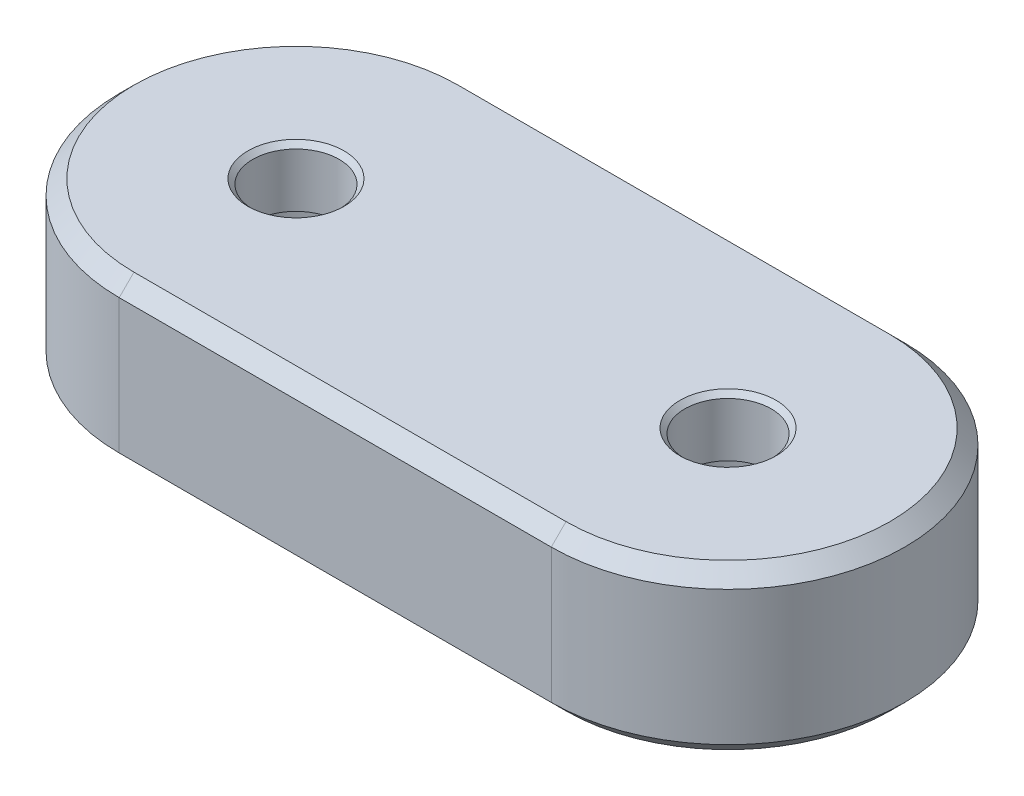
SolidWorks part; units mm, degrees
ref_plane "Front Plane" through (0, 0, 0) normal (0, 0, 1) x (1, 0, 0)
ref_plane "Top Plane" through (0, 0, 0) normal (0, 1, 0) x (1, 0, 0)
ref_plane "Right Plane" through (0, 0, 0) normal (1, 0, 0) x (0, 0, -1)
sketch "Sketch1" plane through (0, 0, 0) normal (0, 1, 0) x (1, 0, 0)
  line L0 (0, 0) -> (22, 0) construction
  line L1 (0, 9) -> (22, 9)
  line L2 (0, -9) -> (22, -9)
  arc A0 (0, 9) -> (0, -9) centre (0, 0) ccw
  arc A1 (22, -9) -> (22, 9) centre (22, 0) ccw
  circle A2 centre (0, 0) radius 2.2
  circle A3 centre (22, 0) radius 2.2
  circle A4 centre (0, 0) radius 4.6
  circle A5 centre (22, 0) radius 4.6
  point P3 (11, 0)
  point P14 (-9, 0)
  point P15 (31, 0)
  dimension "D2" = 4.4
  dimension "D3" = 9.2
  dimension "D1" = 18
  dimension "D4" = 40
extrude "Boss-Extrude1" add sketch "Sketch1" against normal blind 5.35 contours L2 A1 L1 A0 A4 A5 region at (11, 0, 0)
extrude "Boss-Extrude2" add sketch "Sketch1<3>" along normal blind 3 contours L2 A1 L1 A0 A4 A5 | A2 A4 | A5 A3 region at (11, 0, 0) region at (-4.4699, 0, 0) region at (17.5301, 0, 0)
sketch "Sketch1<3>" plane through (0, 0, 0) normal (0, 1, 0) x (1, 0, 0) same geometry as "Sketch1"
chamfer "Chamfer1" distance 0.75 angle 45 10 edges at (22, -5.35, 4.6) (0, -5.35, 4.6) (11, -5.35, -9) (-9, -5.35, 0) (31, -5.35, 0) (11, -5.35, 9) (11, 3, -9) (-9, 3, 0) (31, 3, 0) (11, 3, 9)
chamfer "Chamfer2" distance 0.25 angle 45 2 edges at (22, 3, 2.2) (0, 3, 2.2)
